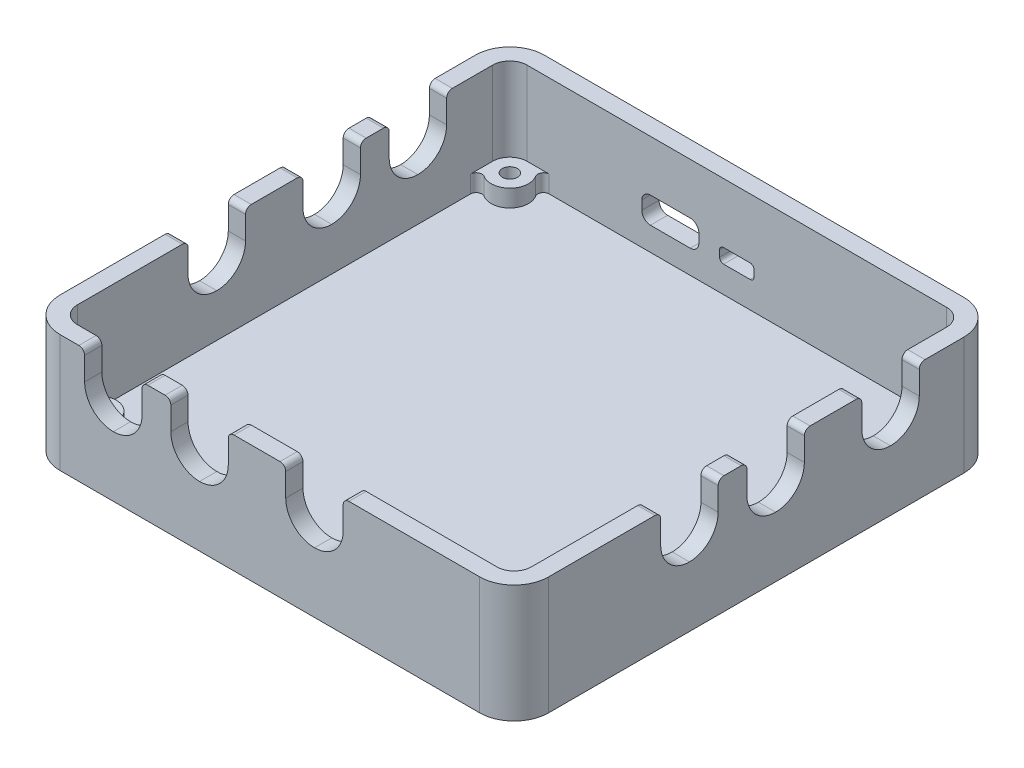
SolidWorks part; units mm, degrees
ref_plane "Front Plane" through (0, 0, 0) normal (0, 0, 1) x (1, 0, 0)
ref_plane "Top Plane" through (0, 0, 0) normal (0, 1, 0) x (1, 0, 0)
ref_plane "Right Plane" through (0, 0, 0) normal (1, 0, 0) x (0, 0, -1)
sketch "Sketch1" plane through (0, 0, 0) normal (0, 1, 0) x (1, 0, 0)
  line L0 (42.5, -42.125) -> (42.5, 42.125)
  line L1 (-36.25, -35.875) -> (36.25, -35.875) construction
  line L2 (-36.25, -35.875) -> (-36.25, 35.875) construction
  line L3 (-36.25, 35.875) -> (36.25, 35.875) construction
  line L4 (36.25, -35.875) -> (36.25, 35.875) construction
  line L5 (-36.25, -35.875) -> (36.25, 35.875) construction
  line L6 (-36.25, 35.875) -> (36.25, -35.875) construction
  line L7 (39.5, -39.125) -> (-39.5, -39.125)
  line L8 (39.5, -39.125) -> (39.5, 39.125)
  line L9 (39.5, 39.125) -> (-39.5, 39.125)
  line L10 (-39.5, -39.125) -> (-39.5, 39.125)
  line L11 (39.5, -39.125) -> (-39.5, 39.125) construction
  line L12 (39.5, 39.125) -> (-39.5, -39.125) construction
  line L13 (42.5, 42.125) -> (-42.5, 42.125)
  line L14 (-42.5, -42.125) -> (-42.5, 42.125)
  line L15 (42.5, -42.125) -> (-42.5, -42.125)
  circle A0 centre (-36.25, 35.875) radius 1.325
  circle A1 centre (36.25, 35.875) radius 1.325
  circle A2 centre (36.25, -35.875) radius 1.325
  circle A3 centre (-36.25, -35.875) radius 1.325
  circle A4 centre (-36.25, 35.875) radius 3.25
  circle A5 centre (-36.25, -35.875) radius 3.25
  circle A6 centre (36.25, -35.875) radius 3.25
  circle A7 centre (36.25, 35.875) radius 3.25
  point P0 (0, 0)
  point P18 (0, 0)
  dimension "D3" = 2.65
  dimension "D1" = 71.75
  dimension "D2" = 72.5
  dimension "D5" = 78.25
  dimension "D6" = 79
  dimension "D7" = 3
extrude "Boss-Extrude1" add sketch "Sketch1" along normal blind 3 contours L15 L14 L13 L0
extrude "Boss-Extrude2" add sketch "Sketch1<3>" along normal blind 3 from surface contours L9 A4 L10 A0 | L7 A6 L8 A2 | L8 A7 L9 A1 | A7 L8 L9 | A6 L7 L8 | L7 A5 L10 A3 | A5 L10 L7 | A4 L9 L10 region at (38.7741, 0, 38.3991) region at (34.0169, 0, 33.6419) region at (-38.7741, 0, 38.3991) region at (-38.4831, 0, 38.1081) region at (38.7741, 0, -38.3991) region at (34.0169, 0, -33.6419) region at (-38.7741, 0, -38.3991) region at (-38.4831, 0, -38.1081) starting at face at (0, 3, 0)
sketch "Sketch1<3>" plane through (0, 0, 0) normal (0, 1, 0) x (1, 0, 0) same geometry as "Sketch1"
extrude "Boss-Extrude6" add sketch "Sketch1<5>" along normal blind 17.5 from surface contours L15 L0 L13 L14 L7 L10 L9 L8 region at (0, 0, 40.9282) starting at face at (37.109, 3, 36.734)
sketch "Sketch1<5>" plane through (0, 0, 0) normal (0, 1, 0) x (1, 0, 0) same geometry as "Sketch1"
fillet "Fillet1" radius 3 4 edges at (-39.5, 13.25, -39.125) (-39.5, 13.25, 39.125) (39.5, 13.25, 39.125) (39.5, 13.25, -39.125)
fillet "Fillet2" radius 6 4 edges at (42.5, 10.25, 42.125) (-42.5, 10.25, 42.125) (-42.5, 10.25, -42.125) (42.5, 10.25, -42.125)
fillet "Fillet3" radius 1 8 edges at (36.25, 4.5, 39.125) (-36.25, 4.5, 39.125) (-39.5, 4.5, 35.875) (-39.5, 4.5, -35.875) (-36.25, 4.5, -39.125) (36.25, 4.5, -39.125) (39.5, 4.5, 35.875) (39.5, 4.5, -35.875)
sketch "Sketch2" plane through (0, 20.5, 0) normal (0, 1, 0) x (1, 0, 0)
  line L0 (-39.5, 36.125) -> (-39.5, -36.125) construction
  line L1 (-42.5, 28.125) -> (-39.5, 28.125)
  line L2 (-42.5, 28.125) -> (-42.5, 18.125)
  line L3 (-42.5, 18.125) -> (-39.5, 18.125)
  line L4 (-39.5, 28.125) -> (-39.5, 18.125)
  line L5 (-42.5, 28.125) -> (-39.5, 18.125) construction
  line L6 (-42.5, 18.125) -> (-39.5, 28.125) construction
  line L7 (-42.5, 36.125) -> (-42.5, -36.125) construction
  line L8 (-42.5, 13.125) -> (-39.5, 13.125)
  line L9 (-42.5, 13.125) -> (-42.5, 3.125)
  line L10 (-42.5, 3.125) -> (-39.5, 3.125)
  line L11 (-39.5, 13.125) -> (-39.5, 3.125)
  line L12 (-42.5, 13.125) -> (-39.5, 3.125) construction
  line L13 (-42.5, 3.125) -> (-39.5, 13.125) construction
  line L14 (-42.5, -6.875) -> (-39.5, -6.875)
  line L15 (-42.5, -6.875) -> (-42.5, -16.875)
  line L16 (-42.5, -16.875) -> (-39.5, -16.875)
  line L17 (-39.5, -6.875) -> (-39.5, -16.875)
  line L18 (-42.5, -6.875) -> (-39.5, -16.875) construction
  line L19 (-42.5, -16.875) -> (-39.5, -6.875) construction
  line L20 (-32.6444, -39.125) -> (32.6444, -39.125) construction
  line L21 (-32.25, -42.125) -> (-22.25, -42.125)
  line L22 (-32.25, -42.125) -> (-32.25, -39.125)
  line L23 (-32.25, -39.125) -> (-22.25, -39.125)
  line L24 (-22.25, -42.125) -> (-22.25, -39.125)
  line L25 (-32.25, -42.125) -> (-22.25, -39.125) construction
  line L26 (-32.25, -39.125) -> (-22.25, -42.125) construction
  line L27 (39.5, 36.125) -> (39.5, -36.125) construction
  line L28 (-17.25, -42.125) -> (-7.25, -42.125)
  line L29 (-17.25, -42.125) -> (-17.25, -39.125)
  line L30 (-17.25, -39.125) -> (-7.25, -39.125)
  line L31 (-7.25, -42.125) -> (-7.25, -39.125)
  line L32 (-17.25, -42.125) -> (-7.25, -39.125) construction
  line L33 (-17.25, -39.125) -> (-7.25, -42.125) construction
  line L34 (2.75, -42.125) -> (12.75, -42.125)
  line L35 (2.75, -42.125) -> (2.75, -39.125)
  line L36 (2.75, -39.125) -> (12.75, -39.125)
  line L37 (12.75, -42.125) -> (12.75, -39.125)
  line L38 (2.75, -42.125) -> (12.75, -39.125) construction
  line L39 (2.75, -39.125) -> (12.75, -42.125) construction
  line L40 (42.5, 18.375) -> (39.5, 18.375)
  line L41 (42.5, 18.375) -> (42.5, 28.375)
  line L42 (42.5, 28.375) -> (39.5, 28.375)
  line L43 (39.5, 18.375) -> (39.5, 28.375)
  line L44 (42.5, 18.375) -> (39.5, 28.375) construction
  line L45 (42.5, 28.375) -> (39.5, 18.375) construction
  line L47 (42.5, 8.375) -> (39.5, 8.375)
  line L48 (42.5, 8.375) -> (42.5, -1.625)
  line L49 (42.5, -1.625) -> (39.5, -1.625)
  line L50 (39.5, 8.375) -> (39.5, -1.625)
  line L51 (42.5, 8.375) -> (39.5, -1.625) construction
  line L52 (42.5, -1.625) -> (39.5, 8.375) construction
  line L53 (42.5, -6.625) -> (39.5, -6.625)
  line L54 (42.5, -6.625) -> (42.5, -16.625)
  line L55 (42.5, -16.625) -> (39.5, -16.625)
  line L56 (39.5, -6.625) -> (39.5, -16.625)
  line L57 (42.5, -6.625) -> (39.5, -16.625) construction
  line L58 (42.5, -16.625) -> (39.5, -6.625) construction
  circle A0 centre (-36.25, -35.875) radius 1.325 construction
  circle A1 centre (-36.25, -35.875) radius 1.325 construction
  circle A2 centre (36.25, -35.875) radius 1.325 construction
  point P0 (-41, 23.125)
  point P7 (-41, 8.125)
  point P12 (-41, -11.875)
  point P23 (-27.25, -40.625)
  point P28 (-12.25, -40.625)
  point P33 (7.75, -40.625)
  point P40 (41, 23.375)
  point P47 (41, 3.375)
  point P52 (41, -11.625)
  point P59 (53.1964, -2.2492)
  dimension "D4" = 24
  dimension "D1" = 15
  dimension "D2" = 20
  dimension "D3" = 10
  dimension "D5" = 15
  dimension "D6" = 20
  dimension "D7" = 9
  dimension "D8" = 20
  dimension "D9" = 15
  dimension "D10" = 24.25
extrude "Cut-Extrude1" cut sketch "Sketch2" against normal blind 10
fillet "Fillet4" radius 5 18 edges at (41, 10.5, 6.625) (41, 10.5, 16.625) (41, 10.5, -8.375) (41, 10.5, 1.625) (41, 10.5, -28.375) (41, 10.5, -18.375) (2.75, 10.5, 40.625) (12.75, 10.5, 40.625) (-17.25, 10.5, 40.625) (-7.25, 10.5, 40.625) (-32.25, 10.5, 40.625) (-22.25, 10.5, 40.625) (-41, 10.5, 16.875) (-41, 10.5, 6.875) (-41, 10.5, -3.125) (-41, 10.5, -18.125) (-41, 10.5, -13.125) (-41, 10.5, -28.125)
fillet "Fillet5" radius 1 18 edges at (-41, 20.5, -18.125) (-41, 20.5, -13.125) (-41, 20.5, -3.125) (-41, 20.5, 6.875) (-41, 20.5, 16.875) (-32.25, 20.5, 40.625) (-22.25, 20.5, 40.625) (-17.25, 20.5, 40.625) (-7.25, 20.5, 40.625) (2.75, 20.5, 40.625) (12.75, 20.5, 40.625) (41, 20.5, 16.625) (41, 20.5, 6.625) (41, 20.5, 1.625) (41, 20.5, -8.375) (41, 20.5, -18.375) (41, 20.5, -28.375) (-41, 20.5, -28.125)
sketch "Sketch4" plane through (0, 0, -42.125) normal (0, 0, -1) x (-1, 0, 0)
  line L0 (37.575, 3) -> (34.925, 3) construction
  line L1 (7.11, 7.6) -> (16.04, 7.6) construction
  line L2 (7.11, 7.6) -> (7.11, 11.14) construction
  line L3 (7.11, 11.14) -> (16.04, 11.14) construction
  line L4 (16.04, 7.6) -> (16.04, 11.14) construction
  line L5 (7.11, 7.6) -> (16.04, 11.14) construction
  line L6 (7.11, 11.14) -> (16.04, 7.6) construction
  line L7 (37.575, 3) -> (34.925, 3) construction
  line L9 (6.61, 7.1) -> (6.61, 11.64)
  line L10 (6.61, 11.64) -> (16.54, 11.64)
  line L11 (16.54, 7.1) -> (16.54, 11.64)
  line L12 (6.61, 7.1) -> (16.54, 7.1)
  line L13 (36.5, 6) -> (32.6444, 6) construction
  point P0 (11.575, 9.37)
  point P7 (36.25, 3)
  point P8 (11.575, 11.1213)
  dimension "D1" = 29.14
  dimension "D2" = 20.21
  dimension "D3" = 3.54
  dimension "D5" = 1.6
  dimension "D4" = 0.5
extrude "Cut-Extrude2" cut sketch "Sketch4" against normal up to next
fillet "Fillet6" radius 1.5 4 edges at (-6.61, 11.64, -40.625) (-16.54, 11.64, -40.625) (-16.54, 7.1, -40.625) (-6.61, 7.1, -40.625)
sketch "Sketch5" plane through (0, 0, -42.125) normal (0, 0, -1) x (-1, 0, 0)
  line L0 (36.5, 6) -> (32.6444, 6) construction
  line L1 (3, 10.1) -> (-3, 10.1)
  line L2 (3, 10.1) -> (3, 7.6)
  line L3 (3, 7.6) -> (-3, 7.6)
  line L4 (-3, 10.1) -> (-3, 7.6)
  line L5 (3, 10.1) -> (-3, 7.6) construction
  line L6 (3, 7.6) -> (-3, 10.1) construction
  line L7 (-42.5, 0) -> (-42.5, 20.5) construction
  point P0 (0, 8.85)
  point P9 (2.0697, 9.7674)
  dimension "D1" = 1.6
  dimension "D2" = 39.5
  dimension "D3" = 6
  dimension "D4" = 2.5
extrude "Cut-Extrude3" cut sketch "Sketch5" against normal up to next
fillet "Fillet7" radius 0.7 4 edges at (-3, 10.1, -40.625) (3, 7.6, -40.625) (3, 10.1, -40.625) (-3, 7.6, -40.625)
